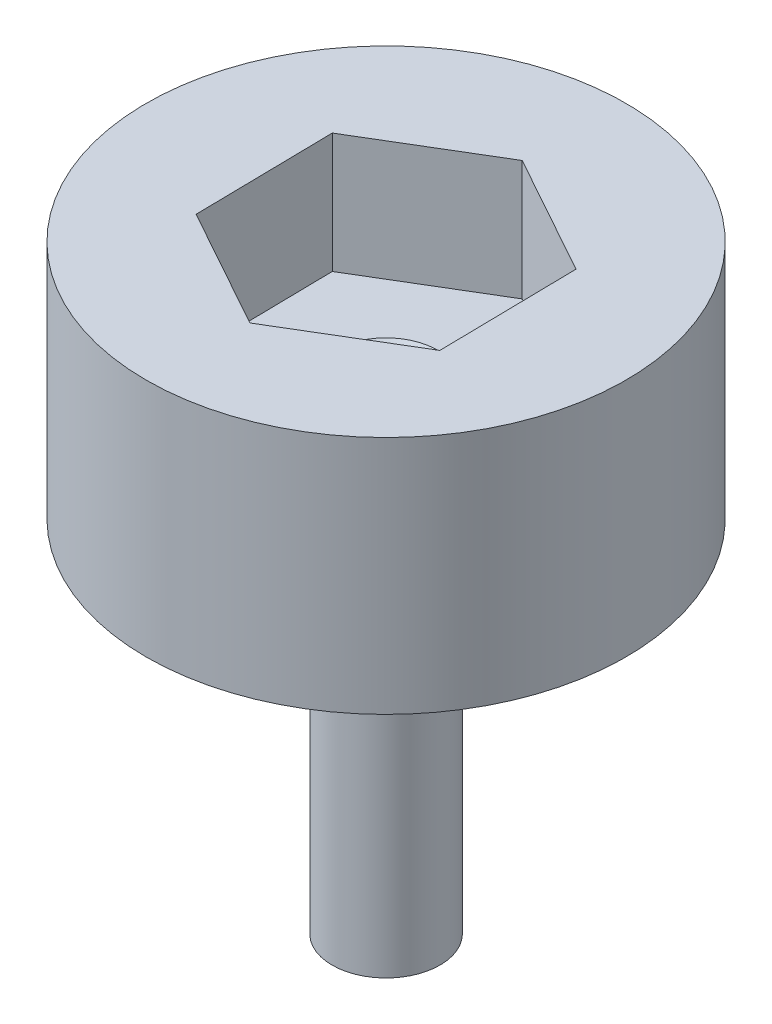
SolidWorks part; units mm, degrees
ref_plane "Front Plane" through (0, 0, 0) normal (0, 0, 1) x (1, 0, 0)
ref_plane "Top Plane" through (0, 0, 0) normal (0, 1, 0) x (1, 0, 0)
ref_plane "Right Plane" through (0, 0, 0) normal (1, 0, 0) x (0, 0, -1)
sketch "Sketch2" plane through (0, 0, 0) normal (0, 1, 0) x (1, 0, 0)
  circle A0 centre (0, 0) radius 20
  dimension "D1" = 40
extrude "Boss-Extrude3" add sketch "Sketch2" along normal blind 20
sketch "Sketch5" plane through (0, 20, 0) normal (0, 1, 0) x (1, 0, 0)
  line L1 (10.0939, -5.6077) -> (9.9034, 5.9377)
  line L2 (9.9034, 5.9377) -> (-0.1905, 11.5454)
  line L3 (-0.1905, 11.5454) -> (-10.0939, 5.6077)
  line L4 (-10.0939, 5.6077) -> (-9.9034, -5.9377)
  line L5 (-9.9034, -5.9377) -> (0.1905, -11.5454)
  line L6 (0.1905, -11.5454) -> (10.0939, -5.6077)
  circle A0 centre (0, 0) radius 10 construction
  point P1 (0, 0)
  dimension "D1" = 10
extrude "Cut-Extrude1" cut sketch "Sketch5" against normal blind 10
sketch "Sketch6" plane through (0, 10, 0) normal (0, 1, 0) x (1, 0, 0)
  circle A0 centre (0, 0) radius 4.5
  dimension "D1" = 9
extrude "Boss-Extrude5" add sketch "Sketch6" against normal blind 40
hole_wizard "M8x1.0 Tapped Hole1" positions "Sketch34" profile "Sketch35" tap size "M8x1.0" standard "GB" end condition through all
sketch "Sketch34" plane through (0, 10, 0) normal (0, 1, 0) x (1, 0, 0)
  point P0 (0, 0)
sketch "Sketch35" plane through (0, 10, 0) normal (1, 0, 0) x (0, 0, 1)
  line L0 (0, 0) -> (0, 40)
  line L1 (0, 40) -> (3.5, 40)
  line L2 (3.5, 40) -> (3.5, 0.825)
  line L3 (3.5, 0.825) -> (4.325, 0)
  line L5 (4.325, 0) -> (0, 0)
  line L6 (-3.5, 0.825) -> (-4.325, 0) construction
  line L11 (0, -6.35) -> (0, 107.95) construction
  dimension "Thru Tap Drill Dia." = 7
  dimension "Thru Tap Drill Depth" = 40
  dimension "Near C'Sink Dia." = 8.65
  dimension "Near C'Sink Angle" = 90
cosmetic thread "Hole Thread2"
thread "Thread8" pitch 1 profile "Thread Profile10" start angle 20, offset 1, length 0, pitch 1, diameter 7
ref_plane "Plane10" through (-3.2889, 8.175, -1.1971) normal (-0.342, 0, 0.9397) x (-0.9397, 0, -0.342)
sketch "Thread Profile10" plane through (-3.2889, 8.175, -1.1971) normal (-0.342, 0, 0.9397) x (-0.9397, 0, -0.342)
  line L0 (0, 0) -> (0, 1) construction
  line L11 (0, 0) -> (0, 0.875)
  line L12 (0, 0.875) -> (-0.5413, 0.5625)
  line L13 (-0.5413, 0.5625) -> (-0.5413, 0.3125)
  line L15 (-0.5413, 0.3125) -> (0, 0)
  line L17 (-0.5413, 0.4375) -> (0, 0.4375) construction
  point P2 (0, 0)
  dimension "Pitch" = 1
  dimension "Profile_Angle" = 60
  dimension "Profile_Land" = 0.25
  dimension "Profile_Height" = 0.5413
